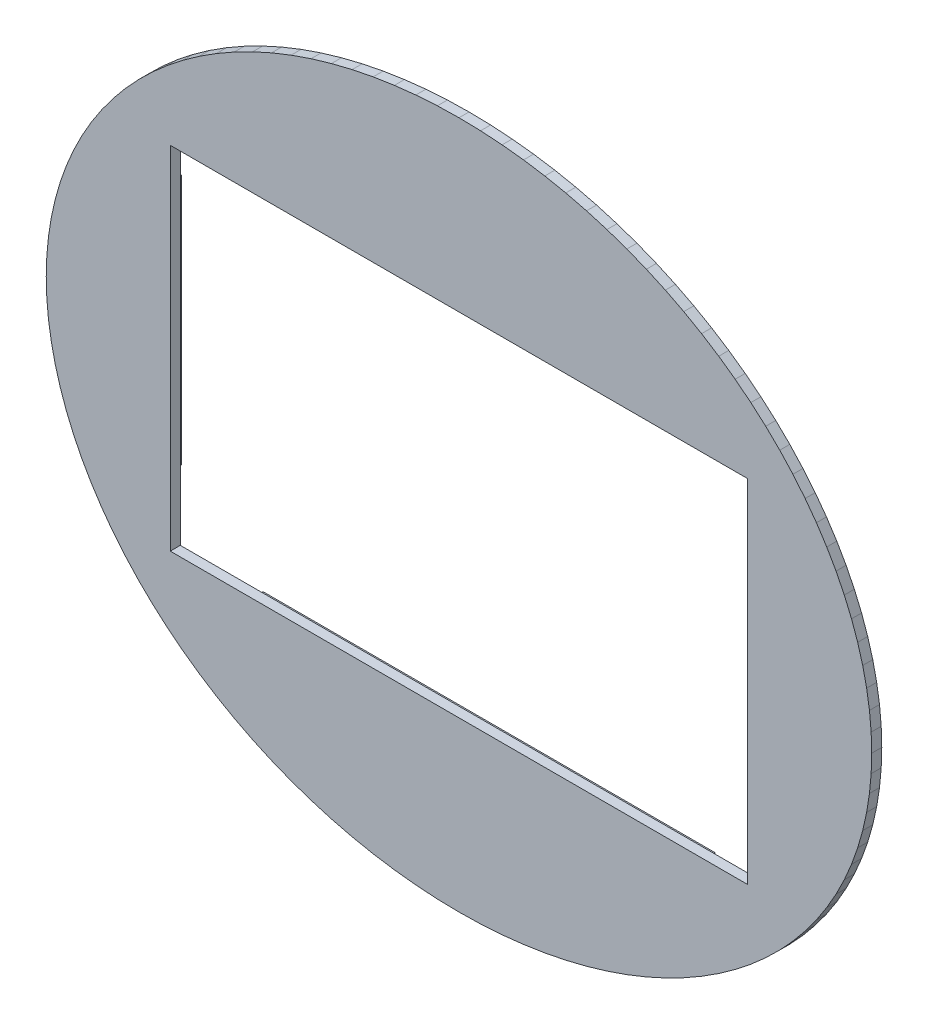
SolidWorks part; units mm, degrees
ref_plane "Front Plane" through (0, 0, 0) normal (0, 0, 1) x (1, 0, 0)
ref_plane "Top Plane" through (0, 0, 0) normal (0, 1, 0) x (1, 0, 0)
ref_plane "Right Plane" through (0, 0, 0) normal (1, 0, 0) x (0, 0, -1)
ref_plane "Plane1" through (0, 0, 66500) normal (0, 0, -1) x (-1, 0, 0)
sketch "Sketch1" plane through (0, 0, 66500) normal (0, 0, -1) x (-1, 0, 0)
  line L0 (41099.9985, 59322.7005) -> (37318.0008, 61033.9012)
  line L1 (37318.0008, 61033.9012) -> (33433.7997, 62577.8999)
  line L2 (33433.7997, 62577.8999) -> (29457.7999, 63950.2983)
  line L3 (29457.7999, 63950.2983) -> (25401.1993, 65147.3999)
  line L4 (25401.1993, 65147.3999) -> (21274.9004, 66165.9012)
  line L5 (21274.9004, 66165.9012) -> (17090.2996, 67003.0975)
  line L6 (17090.2996, 67003.0975) -> (12858.9001, 67656.601)
  line L7 (12858.9001, 67656.601) -> (8592.2403, 68124.7025)
  line L8 (8592.2403, 68124.7025) -> (4302.0201, 68406.0974)
  line L9 (4302.0201, 68406.0974) -> (0, 68500)
  line L10 (0, 68500) -> (-4302.0201, 68406.0974)
  line L11 (-4302.0201, 68406.0974) -> (-8592.2403, 68124.7025)
  line L12 (-8592.2403, 68124.7025) -> (-12858.9001, 67656.601)
  line L13 (-12858.9001, 67656.601) -> (-17090.2996, 67003.0975)
  line L14 (-17090.2996, 67003.0975) -> (-21274.9004, 66165.9012)
  line L15 (-21274.9004, 66165.9012) -> (-25401.1993, 65147.3999)
  line L16 (-25401.1993, 65147.3999) -> (-29457.7999, 63950.2983)
  line L17 (-29457.7999, 63950.2983) -> (-33433.7997, 62577.8999)
  line L18 (-33433.7997, 62577.8999) -> (-37318.0008, 61033.9012)
  line L19 (-37318.0008, 61033.9012) -> (-41099.9985, 59322.7005)
  line L20 (-41099.9985, 59322.7005) -> (-44769.2986, 57448.8983)
  line L21 (-44769.2986, 57448.8983) -> (-48315.8989, 55417.7017)
  line L22 (-48315.8989, 55417.7017) -> (-51730.0987, 53234.5009)
  line L23 (-51730.0987, 53234.5009) -> (-55002.4986, 50905.3993)
  line L24 (-55002.4986, 50905.3993) -> (-58124.1989, 48436.7981)
  line L25 (-58124.1989, 48436.7981) -> (-61086.4983, 45835.3996)
  line L26 (-61086.4983, 45835.3996) -> (-63881.4011, 43108.3984)
  line L27 (-63881.4011, 43108.3984) -> (-66501.1978, 40263.3018)
  line L28 (-66501.1978, 40263.3018) -> (-68938.6978, 37307.8003)
  line L29 (-68938.6978, 37307.8003) -> (-71187.3016, 34250)
  line L30 (-71187.3016, 34250) -> (-73240.6998, 31098.3009)
  line L31 (-73240.6998, 31098.3009) -> (-75093.399, 27861.4998)
  line L32 (-75093.399, 27861.4998) -> (-76740.303, 24548.2006)
  line L33 (-76740.303, 24548.2006) -> (-78176.8036, 21167.6998)
  line L34 (-78176.8036, 21167.6998) -> (-79399.1013, 17729.0993)
  line L35 (-79399.1013, 17729.0993) -> (-80403.7018, 14241.9996)
  line L36 (-80403.7018, 14241.9996) -> (-81188.0035, 10715.8003)
  line L37 (-81188.0035, 10715.8003) -> (-81749.7025, 7160.2001)
  line L38 (-81749.7025, 7160.2001) -> (-82087.3032, 3585.0101)
  line L39 (-82087.3032, 3585.0101) -> (-82199.9969, 0)
  line L40 (-82199.9969, 0) -> (-82087.3032, -3585.0101)
  line L41 (-82087.3032, -3585.0101) -> (-81749.7025, -7160.2001)
  line L42 (-81749.7025, -7160.2001) -> (-81188.0035, -10715.8003)
  line L43 (-81188.0035, -10715.8003) -> (-80403.7018, -14241.9996)
  line L44 (-80403.7018, -14241.9996) -> (-79399.1013, -17729.0993)
  line L45 (-79399.1013, -17729.0993) -> (-78176.8036, -21167.6998)
  line L46 (-78176.8036, -21167.6998) -> (-76740.303, -24548.2006)
  line L47 (-76740.303, -24548.2006) -> (-75093.399, -27861.4998)
  line L48 (-75093.399, -27861.4998) -> (-73240.6998, -31098.3009)
  line L49 (-73240.6998, -31098.3009) -> (-71187.3016, -34250)
  line L50 (-71187.3016, -34250) -> (-68938.6978, -37307.8003)
  line L51 (-68938.6978, -37307.8003) -> (-66501.1978, -40263.3018)
  line L52 (-66501.1978, -40263.3018) -> (-63881.4011, -43108.3984)
  line L53 (-63881.4011, -43108.3984) -> (-61086.4983, -45835.3996)
  line L54 (-61086.4983, -45835.3996) -> (-58124.1989, -48436.7981)
  line L55 (-58124.1989, -48436.7981) -> (-55002.4986, -50905.3993)
  line L56 (-55002.4986, -50905.3993) -> (-51730.0987, -53234.5009)
  line L57 (-51730.0987, -53234.5009) -> (-48315.8989, -55417.7017)
  line L58 (-48315.8989, -55417.7017) -> (-44769.2986, -57448.8983)
  line L59 (-44769.2986, -57448.8983) -> (-41099.9985, -59322.7005)
  line L60 (-41099.9985, -59322.7005) -> (-37318.0008, -61033.9012)
  line L61 (-37318.0008, -61033.9012) -> (-33433.7997, -62577.8999)
  line L62 (-33433.7997, -62577.8999) -> (-29457.7999, -63950.2983)
  line L63 (-29457.7999, -63950.2983) -> (-25401.1993, -65147.3999)
  line L64 (-25401.1993, -65147.3999) -> (-21274.9004, -66165.9012)
  line L65 (-21274.9004, -66165.9012) -> (-17090.2996, -67003.0975)
  line L66 (-17090.2996, -67003.0975) -> (-12858.9001, -67656.601)
  line L67 (-12858.9001, -67656.601) -> (-8592.2403, -68124.7025)
  line L68 (-8592.2403, -68124.7025) -> (-4302.0201, -68406.0974)
  line L69 (-4302.0201, -68406.0974) -> (0, -68500)
  line L70 (0, -68500) -> (4302.0201, -68406.0974)
  line L71 (4302.0201, -68406.0974) -> (8592.2403, -68124.7025)
  line L72 (8592.2403, -68124.7025) -> (12858.9001, -67656.601)
  line L73 (12858.9001, -67656.601) -> (17090.2996, -67003.0975)
  line L74 (17090.2996, -67003.0975) -> (21274.9004, -66165.9012)
  line L75 (21274.9004, -66165.9012) -> (25401.1993, -65147.3999)
  line L76 (25401.1993, -65147.3999) -> (29457.7999, -63950.2983)
  line L77 (29457.7999, -63950.2983) -> (33433.7997, -62577.8999)
  line L78 (33433.7997, -62577.8999) -> (37318.0008, -61033.9012)
  line L79 (37318.0008, -61033.9012) -> (41099.9985, -59322.7005)
  line L80 (41099.9985, -59322.7005) -> (44769.2986, -57448.8983)
  line L81 (44769.2986, -57448.8983) -> (48315.8989, -55417.7017)
  line L82 (48315.8989, -55417.7017) -> (51730.0987, -53234.5009)
  line L83 (51730.0987, -53234.5009) -> (55002.4986, -50905.3993)
  line L84 (55002.4986, -50905.3993) -> (58124.1989, -48436.7981)
  line L85 (58124.1989, -48436.7981) -> (61086.4983, -45835.3996)
  line L86 (61086.4983, -45835.3996) -> (63881.4011, -43108.3984)
  line L87 (63881.4011, -43108.3984) -> (66501.1978, -40263.3018)
  line L88 (66501.1978, -40263.3018) -> (68938.6978, -37307.8003)
  line L89 (68938.6978, -37307.8003) -> (71187.3016, -34250)
  line L90 (71187.3016, -34250) -> (73240.6998, -31098.3009)
  line L91 (73240.6998, -31098.3009) -> (75093.399, -27861.4998)
  line L92 (75093.399, -27861.4998) -> (76740.303, -24548.2006)
  line L93 (76740.303, -24548.2006) -> (78176.8036, -21167.6998)
  line L94 (78176.8036, -21167.6998) -> (79399.1013, -17729.0993)
  line L95 (79399.1013, -17729.0993) -> (80403.7018, -14241.9996)
  line L96 (80403.7018, -14241.9996) -> (81188.0035, -10715.8003)
  line L97 (81188.0035, -10715.8003) -> (81749.7025, -7160.2001)
  line L98 (81749.7025, -7160.2001) -> (82087.3032, -3585.0101)
  line L99 (82087.3032, -3585.0101) -> (82199.9969, 0)
  line L100 (82199.9969, 0) -> (82087.3032, 3585.0101)
  line L101 (82087.3032, 3585.0101) -> (81749.7025, 7160.2001)
  line L102 (81749.7025, 7160.2001) -> (81188.0035, 10715.8003)
  line L103 (81188.0035, 10715.8003) -> (80403.7018, 14241.9996)
  line L104 (80403.7018, 14241.9996) -> (79399.1013, 17729.0993)
  line L105 (79399.1013, 17729.0993) -> (78176.8036, 21167.6998)
  line L106 (78176.8036, 21167.6998) -> (76740.303, 24548.2006)
  line L107 (76740.303, 24548.2006) -> (75093.399, 27861.4998)
  line L108 (75093.399, 27861.4998) -> (73240.6998, 31098.3009)
  line L109 (73240.6998, 31098.3009) -> (71187.3016, 34250)
  line L110 (71187.3016, 34250) -> (68938.6978, 37307.8003)
  line L111 (68938.6978, 37307.8003) -> (66501.1978, 40263.3018)
  line L112 (66501.1978, 40263.3018) -> (63881.4011, 43108.3984)
  line L113 (63881.4011, 43108.3984) -> (61086.4983, 45835.3996)
  line L114 (61086.4983, 45835.3996) -> (58124.1989, 48436.7981)
  line L115 (58124.1989, 48436.7981) -> (55002.4986, 50905.3993)
  line L116 (55002.4986, 50905.3993) -> (51730.0987, 53234.5009)
  line L117 (51730.0987, 53234.5009) -> (48315.8989, 55417.7017)
  line L118 (48315.8989, 55417.7017) -> (44769.2986, 57448.8983)
  line L119 (44769.2986, 57448.8983) -> (41099.9985, 59322.7005)
extrude "Boss-Extrude1" add sketch "Sketch1" against normal blind 2000
sketch "Sketch2" plane through (0, 0, 68500) normal (0, 0, 1) x (1, 0, 0)
  line L0 (-57500, -35000) -> (57500, -35000)
  line L1 (57500, -35000) -> (57500, 35000)
  line L2 (57500, 35000) -> (-57500, 35000)
  line L3 (-57500, 35000) -> (-57500, -35000)
extrude "Cut-Extrude1" cut sketch "Sketch2" against normal through all
sketch "Sketch3" plane through (0, 0, 66500) normal (0, 0, -1) x (-1, 0, 0)
  line L0 (61250, -25000) -> (61250, 25000)
  line L1 (61250, 25000) -> (63500, 25000)
  line L2 (63500, 25000) -> (63500, -25000)
  line L3 (63500, -25000) -> (61250, -25000)
extrude "Boss-Extrude2" add sketch "Sketch3" along normal blind 4000
sketch "Sketch4" plane through (0, 0, 66500) normal (0, 0, -1) x (-1, 0, 0)
  line L0 (-45000, 38750) -> (-45000, 41000)
  line L1 (-45000, 41000) -> (45000, 41000)
  line L2 (45000, 41000) -> (45000, 38750)
  line L3 (45000, 38750) -> (-45000, 38750)
extrude "Boss-Extrude3" add sketch "Sketch4" along normal blind 4000
sketch "Sketch5" plane through (0, 0, 66500) normal (0, 0, -1) x (-1, 0, 0)
  line L0 (-45000, -41000) -> (-45000, -38750)
  line L1 (-45000, -38750) -> (45000, -38750)
  line L2 (45000, -38750) -> (45000, -41000)
  line L3 (45000, -41000) -> (-45000, -41000)
extrude "Boss-Extrude4" add sketch "Sketch5" along normal blind 4000
sketch "Sketch6" plane through (0, 0, 66500) normal (0, 0, -1) x (-1, 0, 0)
  line L0 (-63500, -25000) -> (-63500, 25000)
  line L1 (-63500, 25000) -> (-61250, 25000)
  line L2 (-61250, 25000) -> (-61250, -25000)
  line L3 (-61250, -25000) -> (-63500, -25000)
extrude "Boss-Extrude5" add sketch "Sketch6" along normal blind 4000
scale "Scale4" scale about centroid uniform scaling yes scale factor 0.001
sketch "Sketch17" plane through (0, 0, 67152.2803) normal (0, 0, -1) x (-1, 0, 0)
  line L1 (-61.25, -25) -> (-65.25, -25)
  line L2 (-61.25, -25) -> (-61.25, 25)
  line L3 (-61.25, 25) -> (-65.25, 25)
  line L4 (-65.25, -25) -> (-65.25, 25)
  dimension "D1" = 50
  dimension "D2" = 4
extrude "Boss-Extrude7" add sketch "Sketch17" along normal blind 4 contours L2 L1 L4 L3
sketch "Sketch18" plane through (0, 0, 67148.2803) normal (0, 0, -1) x (-1, 0, 0)
  line L0 (-61.25, -25) -> (-61.25, 25) construction
  line L1 (-61.25, 25) -> (-65.25, 25) construction
  circle A0 centre (-63.25, 0) radius 1.25
  dimension "D1" = 2.5
  dimension "D2" = 2
  dimension "D3" = 25
hole_wizard "#40 (0.098) Diameter Hole1" positions "Sketch19" profile "Sketch20" hole size "#40" standard "ANSI Inch"
sketch "Sketch19" plane through (0, 0, 67148.2803) normal (0, 0, -1) x (-1, 0, 0)
  point P0 (-63.25, 0)
sketch "Sketch20" plane through (63.25, 0, 67148.2803) normal (1, 0, 0) x (0, 1, 0)
  line L0 (0, 0) -> (0, 3.7511)
  line L1 (0, 3.7511) -> (1.25, 3)
  line L2 (1.25, 3) -> (1.25, 0)
  line L5 (1.25, 0) -> (0, 0)
  line L10 (0, 3.7511) -> (-1.25, 3) construction
  line L11 (0, -6.35) -> (0, 107.95) construction
  dimension "Hole Dia." = 2.5
  dimension "Hole Depth" = 3
  dimension "Drill Angle" = 118
sketch "Sketch21" plane through (0, 0, 67152.2803) normal (0, 0, -1) x (-1, 0, 0)
  line L1 (-45, 38.75) -> (45, 38.75)
  line L2 (-45, 38.75) -> (-45, 42.75)
  line L3 (-45, 42.75) -> (45, 42.75)
  line L4 (45, 38.75) -> (45, 42.75)
  dimension "D1" = 90
  dimension "D2" = 4
extrude "Boss-Extrude8" add sketch "Sketch21" along normal blind 4
sketch "Sketch22" plane through (0, 0, 67152.2803) normal (0, 0, -1) x (-1, 0, 0)
  line L1 (61.25, -25) -> (65.25, -25)
  line L2 (61.25, -25) -> (61.25, 25)
  line L3 (61.25, 25) -> (65.25, 25)
  line L4 (65.25, -25) -> (65.25, 25)
  dimension "D1" = 50
  dimension "D2" = 4
extrude "Boss-Extrude9" add sketch "Sketch22" along normal blind 4
sketch "Sketch23" plane through (0, 0, 67152.2803) normal (0, 0, -1) x (-1, 0, 0)
  line L1 (-45, -38.75) -> (45, -38.75)
  line L2 (-45, -38.75) -> (-45, -42.75)
  line L3 (-45, -42.75) -> (45, -42.75)
  line L4 (45, -38.75) -> (45, -42.75)
  dimension "D1" = 90
  dimension "D2" = 4
extrude "Boss-Extrude10" add sketch "Sketch23" along normal blind 4
